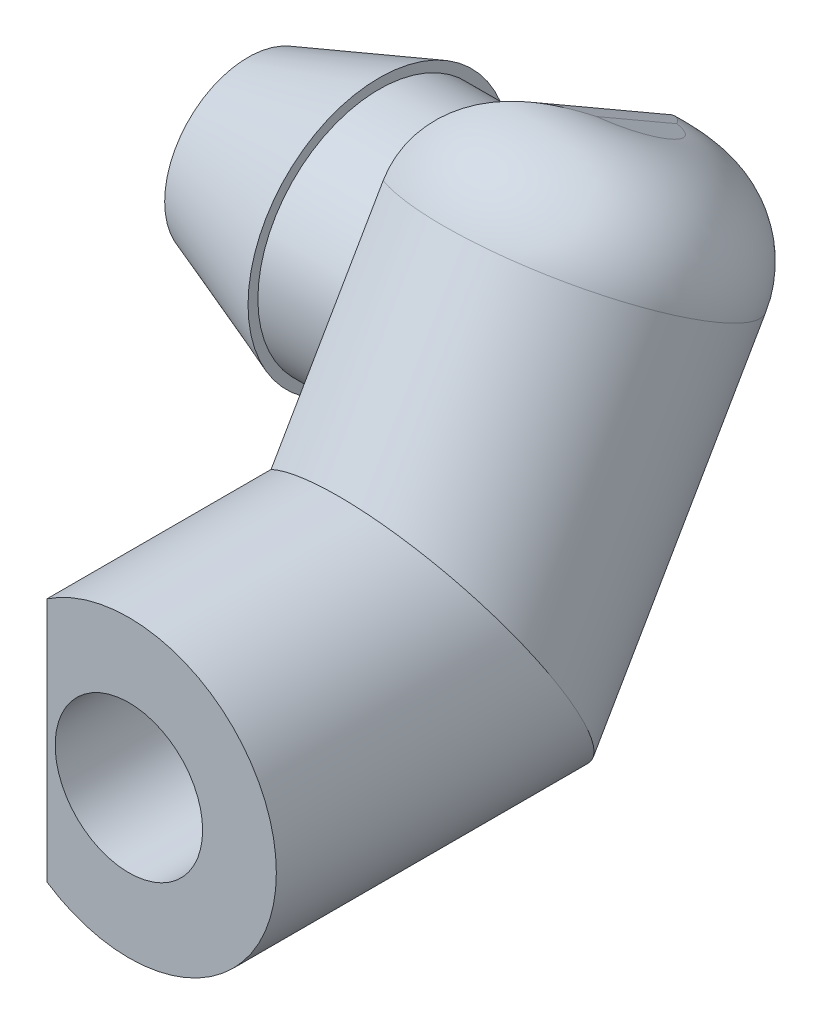
SolidWorks part; units mm, degrees
ref_plane "Front Plane" through (0, 0, 0) normal (0, 0, 1) x (1, 0, 0)
ref_plane "Top Plane" through (0, 0, 0) normal (0, 1, 0) x (1, 0, 0)
ref_plane "Right Plane" through (0, 0, 0) normal (1, 0, 0) x (0, 0, -1)
sketch "Sketch1" plane through (0, 0, 0) normal (0, 0, 1) x (1, 0, 0)
  line L0 (-1.25, 1.8708) -> (-1.25, -1.8708)
  arc A0 (-1.25, -1.8708) -> (-1.25, 1.8708) centre (0, 0) ccw
  point P5 (0, 0)
  dimension "D1" = 4.5
  dimension "D2" = 1.25
sketch "Sketch2" plane through (0, 0, 0) normal (1, 0, 0) x (0, 0, -1)
  line L0 (0, 0) -> (4.5, 0)
  line L1 (4.5, 0) -> (7.5, 5.1962)
  dimension "D1" = 4.5
  dimension "D2" = 6
  dimension "D3" = 120
sweep "Sweep1" add profiles "Sketch1" path "Sketch2"
fillet "Fillet1" radius 1.5 2 edges at (2.25, 5.1962, -7.5) (-1.25, 5.1962, -7.5)
sketch "Sketch3" plane through (0, 0, 0) normal (0, 0, 1) x (1, 0, 0)
  circle A0 centre (0, 0) radius 1.125
  dimension "D1" = 2.25
extrude "Cut-Extrude1" cut sketch "Sketch3" against normal blind 5.7
sketch "Sketch4" plane through (-1.25, 0, 0) normal (-1, 0, 0) x (0, 0, 1)
  line L0 (-6.268, 8.2578) -> (-6.268, -2.2164) construction
  line L1 (-9.9806, 3.0207) -> (-3.4751, 3.0207) construction
  line L2 (-8.1124, 4.8426) -> (-6.8876, 5.5497) construction
  line L3 (-5.5801, -1.8708) -> (-8.3702, 2.9617) construction
  circle A0 centre (-6.268, 3.0207) radius 1.85
  point P6 (-6.268, 3.0207)
  point P9 (-6.7714, 2.73)
  point P10 (-5.7542, 3.3173)
  dimension "D1" = 3.7
  dimension "D2" = 2.5
extrude "Boss-Extrude1" add sketch "Sketch4" along normal blind 1.2 and the other way up to surface other way up to face at (-0.5971, 4.7265, -7.2289)
sketch "Sketch5" plane through (-2.45, 0, 0) normal (-1, 0, 0) x (0, 0, 1)
  circle A2 centre (-6.268, 3.0207) radius 2
  circle A3 centre (-6.268, 3.0207) radius 2
  dimension "D1" = 0.15
extrude "Boss-Extrude2" add sketch "Sketch5" along normal blind 2 draft 20
sketch "Sketch8" plane through (-4.45, 0, 0) normal (-1, 0, 0) x (0, 0, 1)
  circle A0 centre (-6.268, 3.0207) radius 0.85
  dimension "D1" = 1.7
extrude "Cut-Extrude2" cut sketch "Sketch8" against normal blind 2.4
ref_plane "Plane1" through (0, 0, -8.118) normal (0, 0, -1) x (-1, 0, 0)
sketch "Sketch7" plane through (0, 0, -8.118) normal (0, 0, -1) x (-1, 0, 0)
  line L0 (2.45, 2.6707) -> (4.45, 2.6707)
  line L1 (2.45, 5.0207) -> (2.45, 1.0207) construction
  line L2 (4.45, 1.7486) -> (4.45, 4.2927) construction
  line L3 (4.45, 2.6707) -> (4.45, 3.3707)
  line L4 (4.45, 3.3707) -> (2.45, 3.3707)
  line L5 (2.45, 4.8707) -> (2.45, 1.1707) construction
  line L6 (2.45, 3.3707) -> (2.45, 2.6707)
  line L7 (2.45, 3.0207) -> (-6.6385, 3.0207) construction
  point P12 (2.45, 3.0207)
  dimension "D1" = 0.7
extrude "Cut-Extrude5" cut sketch "Sketch7" against normal mid plane 3.4 contours L6 L0 L3 L4
